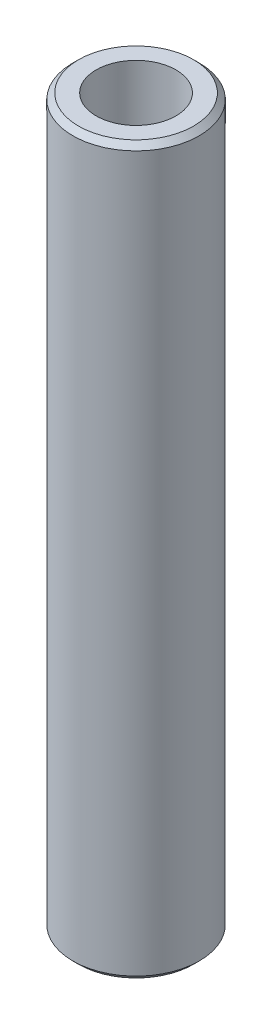
SolidWorks part; units mm, degrees
ref_plane "Front Plane" through (0, 0, 0) normal (0, 0, 1) x (1, 0, 0)
ref_plane "Top Plane" through (0, 0, 0) normal (0, 1, 0) x (1, 0, 0)
ref_plane "Right Plane" through (0, 0, 0) normal (1, 0, 0) x (0, 0, -1)
sketch "Sketch1" plane through (0, 0, 0) normal (0, 1, 0) x (1, 0, 0)
  circle A0 centre (0, 0) radius 10
  dimension "SHAFT_OD" = 20
extrude "Boss-Extrude1" add sketch "Sketch1" along normal blind 114.9498
sketch "Sketch2" plane through (0, 0, 0) normal (0, 1, 0) x (1, 0, 0)
  circle A0 centre (0, 0) radius 6.3195
  dimension "BORE_D" = 12.639
extrude "Cut-Extrude1" cut sketch "Sketch2" along normal through all
chamfer "Chamfer1" distance 0.889 angle 45 2 edges at (0, 114.9498, 10) (0, 0, 10)
